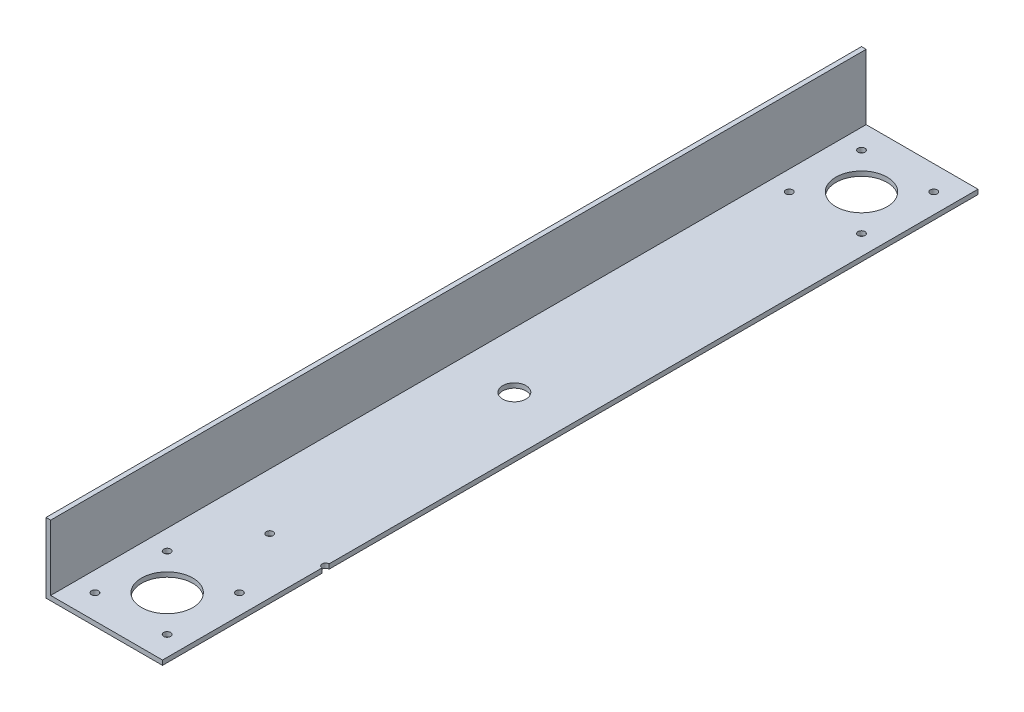
SolidWorks part; units mm, degrees
ref_plane "Front Plane" through (0, 0, 0) normal (0, 0, 1) x (1, 0, 0)
ref_plane "Top Plane" through (0, 0, 0) normal (0, 1, 0) x (1, 0, 0)
ref_plane "Right Plane" through (0, 0, 0) normal (1, 0, 0) x (0, 0, -1)
sketch "Sketch1" plane through (0, 0, 0) normal (0, 0, 1) x (1, 0, 0)
  line L0 (0, 0) -> (0, 30)
  line L1 (0, 30) -> (2, 30)
  line L2 (2, 30) -> (2, 2)
  line L3 (2, 2) -> (50, 2)
  line L4 (50, 2) -> (50, 0)
  line L5 (50, 0) -> (0, 0)
extrude "Boss-Extrude1" add sketch "Sketch1" along normal blind 350
sketch "Sketch6" plane through (0, 2, 0) normal (0, 1, 0) x (1, 0, 0)
  circle A0 centre (41.5, -339.5) radius 1.5
  circle A1 centre (10.5, -308.5) radius 1.5
  circle A2 centre (10.5, -339.5) radius 1.5
  circle A3 centre (41.5, -308.5) radius 1.5
extrude "Cut-Extrude3" cut sketch "Sketch6" against normal through all
sketch "Sketch7" plane through (0, 2, 0) normal (0, 1, 0) x (1, 0, 0)
  circle A0 centre (26, -324) radius 11
extrude "Cut-Extrude4" cut sketch "Sketch7" against normal through all
sketch "Sketch8" plane through (0, 0, 0) normal (0, -1, 0) x (-1, 0, 0)
  circle A0 centre (-26, -26) radius 11
extrude "Cut-Extrude5" cut sketch "Sketch8" against normal through all
sketch "Sketch9" plane through (0, 0, 0) normal (0, -1, 0) x (1, 0, 0)
  circle A0 centre (41.5, 41.5) radius 1.5
  circle A1 centre (10.5, 41.5) radius 1.5
  circle A2 centre (10.5, 10.5) radius 1.5
  circle A3 centre (41.5, 10.5) radius 1.5
extrude "Cut-Extrude6" cut sketch "Sketch9" against normal through all
sketch "Sketch10" plane through (0, 0, 0) normal (0, -1, 0) x (1, 0, 0)
  circle A0 centre (26, 175) radius 5
extrude "Cut-Extrude7" cut sketch "Sketch10" against normal through all
hole_wizard "Ø3.0 (3) Diameter Hole1" positions "Sketch11" profile "Sketch12" hole size "Ø3.0" standard "ISO" end condition through all
sketch "Sketch11" plane through (-11.4076, 2, 221.138) normal (0, 1, 0) x (0, 0, 1)
  point P0 (58.862, 61.4076)
  point P1 (58.862, 37.4076)
sketch "Sketch12" plane through (50, 2, 280) normal (1, 0, 0) x (0, 0, 1)
  line L0 (0, 0) -> (0, 2)
  line L1 (0, 2) -> (1.5, 2)
  line L2 (1.5, 2) -> (1.5, 0)
  line L3 (1.5, 0) -> (0, 0)
  line L4 (0, -6.35) -> (0, 107.95) construction
  dimension "Thru Hole Dia." = 3
  dimension "Thru Hole Depth" = 2
